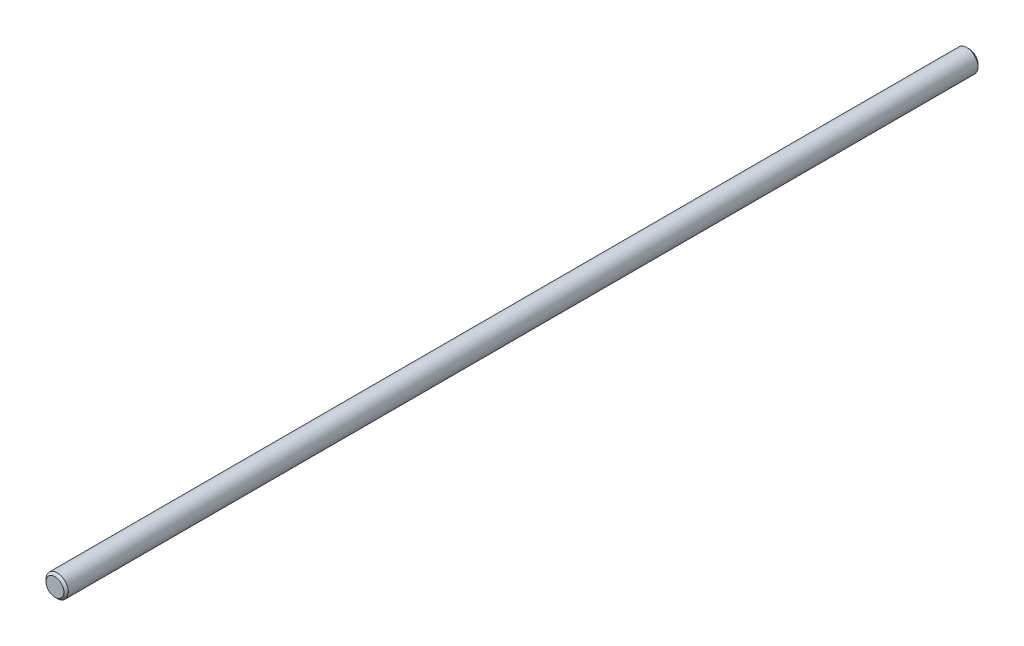
SolidWorks part; units mm, degrees
ref_plane "Piano frontale" through (0, 0, 0) normal (0, 0, 1) x (1, 0, 0)
ref_plane "Piano superiore" through (0, 0, 0) normal (0, 1, 0) x (1, 0, 0)
ref_plane "Piano destro" through (0, 0, 0) normal (1, 0, 0) x (0, 0, -1)
sketch "Schizzo1" plane through (0, 0, 0) normal (0, 0, 1) x (1, 0, 0)
  circle A0 centre (0, 0) radius 5
  dimension "D1" = 10
extrude "Estrusione-Estrusione1" add sketch "Schizzo1" along normal blind 410
chamfer "Smusso1" distance 1 angle 45 2 edges at (5, 0, 410) (5, 0, 0)
